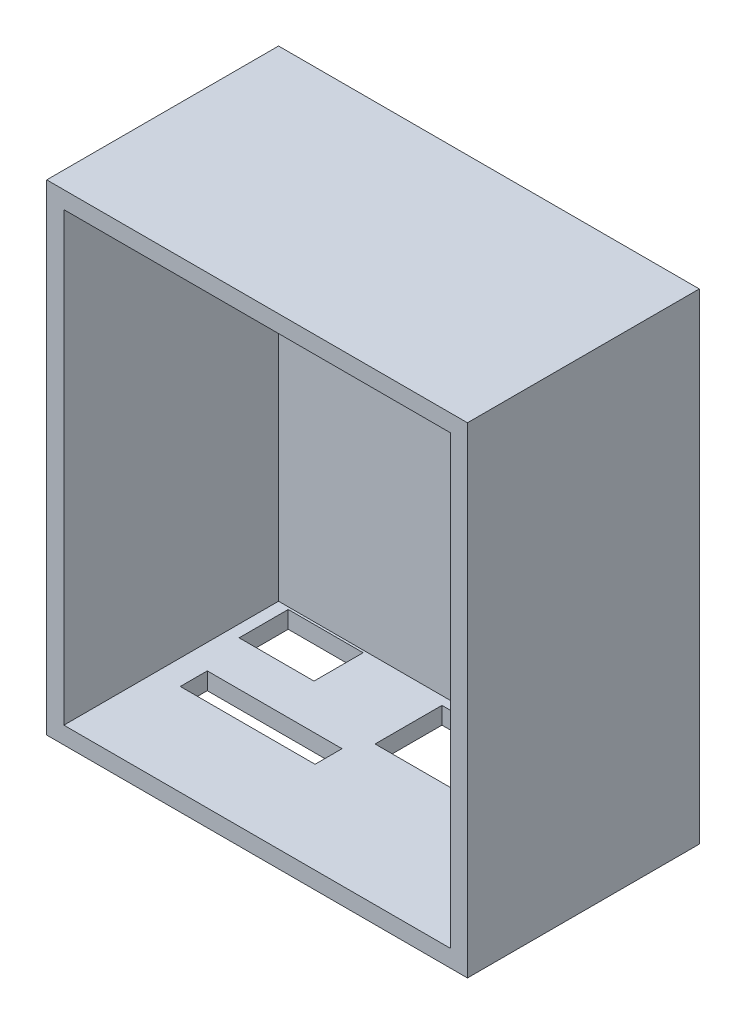
SolidWorks part; units mm, degrees
ref_plane "Piano frontale" through (0, 0, 0) normal (0, 0, 1) x (1, 0, 0)
ref_plane "Piano superiore" through (0, 0, 0) normal (0, 1, 0) x (1, 0, 0)
ref_plane "Piano destro" through (0, 0, 0) normal (1, 0, 0) x (0, 0, -1)
sketch "Schizzo1" plane through (0, 0, 0) normal (0, 0, 1) x (1, 0, 0)
  line L1 (0, 0) -> (49, 0)
  line L2 (0, 0) -> (0, 56)
  line L3 (0, 56) -> (49, 56)
  line L4 (49, 0) -> (49, 56)
  dimension "D1" = 49
  dimension "D2" = 56
extrude "Estrusione-Estrusione1" add sketch "Schizzo1" along normal blind 2
sketch "Schizzo3" plane through (0, 0, 2) normal (0, 0, 1) x (1, 0, 0)
  line L0 (49, 0) -> (49, 56) construction
  line L1 (0, 56) -> (49, 56)
  line L2 (0, 56) -> (0, 54)
  line L3 (0, 54) -> (49, 54)
  line L4 (49, 56) -> (49, 54)
  dimension "D1" = 2
extrude "Estrusione-Estrusione2" add sketch "Schizzo3" along normal blind 25
sketch "Schizzo4" plane through (0, 0, 2) normal (0, 0, 1) x (1, 0, 0)
  line L0 (0, 0) -> (49, 0) construction
  line L1 (49, 54) -> (47, 54)
  line L2 (49, 54) -> (49, 0)
  line L3 (49, 0) -> (47, 0)
  line L4 (47, 54) -> (47, 0)
  dimension "D1" = 2
extrude "Estrusione-Estrusione3" add sketch "Schizzo4" along normal blind 25
sketch "Schizzo5" plane through (0, 0, 2) normal (0, 0, 1) x (1, 0, 0)
  line L0 (0, 54) -> (0, 0) construction
  line L1 (47, 0) -> (0, 0)
  line L2 (47, 0) -> (47, 2)
  line L3 (47, 2) -> (0, 2)
  line L4 (0, 0) -> (0, 2)
  dimension "D1" = 2
extrude "Estrusione-Estrusione4" add sketch "Schizzo5" along normal blind 25
sketch "Schizzo6" plane through (0, 0, 2) normal (0, 0, 1) x (1, 0, 0)
  line L0 (47, 2) -> (0, 2) construction
  line L1 (0, 54) -> (2, 54)
  line L2 (0, 54) -> (0, 2)
  line L3 (0, 2) -> (2, 2)
  line L4 (2, 54) -> (2, 2)
  dimension "D1" = 2
extrude "Estrusione-Estrusione5" add sketch "Schizzo6" along normal blind 25
sketch "Schizzo7" plane through (0, 0, 2) normal (0, 0, 1) x (1, 0, 0)
  line L1 (2, 2) -> (2, 54) construction
  line L4 (2, 43.7) -> (27, 43.7)
  line L5 (2, 43.7) -> (2, 46.7)
  line L6 (2, 46.7) -> (27, 46.7)
  line L7 (27, 43.7) -> (27, 46.7)
  dimension "D2" = 3
  dimension "D3" = 25
extrude "Estrusione-Estrusione6" add sketch "Schizzo7" along normal blind 13.3
sketch "Schizzo9" plane through (0, 0, 2) normal (0, 0, 1) x (1, 0, 0)
  line L0 (2, 54) -> (47, 54) construction
  line L1 (47, 2) -> (43.5, 2)
  line L2 (47, 2) -> (47, 54)
  line L3 (47, 54) -> (43.5, 54)
  line L4 (43.5, 2) -> (43.5, 54)
  dimension "D1" = 3.5
extrude "Estrusione-Estrusione7" add sketch "Schizzo9" along normal blind 13.3
sketch "Schizzo10" plane through (0, 0, 15.3) normal (0, 0, 1) x (1, 0, 0)
  line L5 (4, 45.95) -> (8, 45.95)
  line L6 (4, 45.95) -> (4, 44.45)
  line L7 (4, 44.45) -> (8, 44.45)
  line L8 (8, 45.95) -> (8, 44.45)
  line L11 (26, 45.95) -> (22, 45.95)
  line L12 (26, 45.95) -> (26, 44.45)
  line L13 (26, 44.45) -> (22, 44.45)
  line L14 (22, 45.95) -> (22, 44.45)
  point P17 (26, 45.2)
  dimension "D3" = 1.5
  dimension "D4" = 4
  dimension "D6" = 4
extrude "Taglio-Estrusione1" cut sketch "Schizzo10" against normal blind 6
sketch "Schizzo11" plane through (0, 0, 15.3) normal (0, 0, 1) x (1, 0, 0)
  line L4 (46, 45.95) -> (44.5, 45.95)
  line L5 (46, 45.95) -> (46, 44.45)
  line L6 (46, 44.45) -> (44.5, 44.45)
  line L7 (44.5, 45.95) -> (44.5, 44.45)
  dimension "D2" = 1.5
  dimension "D3" = 1.5
extrude "Taglio-Estrusione2" cut sketch "Schizzo11" against normal blind 6
sketch "Schizzo12" plane through (0, 45.95, 0) normal (0, -1, 0) x (-1, 0, 0)
  line L0 (-8, -9.3) -> (-8, -15.3) construction
  line L1 (-4, -15.3) -> (-8, -15.3)
  line L2 (-4, -15.3) -> (-4, -14.3)
  line L3 (-4, -14.3) -> (-8, -14.3)
  line L4 (-8, -15.3) -> (-8, -14.3)
  dimension "D1" = 1
extrude "Taglio-Estrusione3" cut sketch "Schizzo12" against normal blind 0.75
sketch "Schizzo13" plane through (0, 44.45, 0) normal (0, 1, 0) x (1, 0, 0)
  line L0 (8, -9.3) -> (8, -15.3) construction
  line L1 (4, -15.3) -> (8, -15.3)
  line L2 (4, -15.3) -> (4, -14.3)
  line L3 (4, -14.3) -> (8, -14.3)
  line L4 (8, -15.3) -> (8, -14.3)
  dimension "D1" = 1
extrude "Taglio-Estrusione4" cut sketch "Schizzo13" against normal blind 0.75
sketch "Schizzo14" plane through (0, 45.95, 0) normal (0, -1, 0) x (-1, 0, 0)
  line L0 (-26, -9.3) -> (-26, -15.3) construction
  line L1 (-22, -15.3) -> (-26, -15.3)
  line L2 (-22, -15.3) -> (-22, -14.3)
  line L3 (-22, -14.3) -> (-26, -14.3)
  line L4 (-26, -15.3) -> (-26, -14.3)
  dimension "D1" = 1
extrude "Taglio-Estrusione5" cut sketch "Schizzo14" against normal blind 0.75
sketch "Schizzo15" plane through (0, 44.45, 0) normal (0, 1, 0) x (1, 0, 0)
  line L0 (26, -9.3) -> (26, -15.3) construction
  line L1 (22, -15.3) -> (26, -15.3)
  line L2 (22, -15.3) -> (22, -14.3)
  line L3 (22, -14.3) -> (26, -14.3)
  line L4 (26, -15.3) -> (26, -14.3)
  dimension "D1" = 1
extrude "Taglio-Estrusione6" cut sketch "Schizzo15" against normal blind 0.75
sketch "Schizzo21" plane through (0, 0, 15.3) normal (0, 0, 1) x (1, 0, 0)
  line L0 (43.5, 54) -> (43.5, 2) construction
  line L1 (44.5, 45.95) -> (43.5, 45.95)
  line L2 (44.5, 45.95) -> (44.5, 44.45)
  line L3 (44.5, 44.45) -> (43.5, 44.45)
  line L4 (43.5, 45.95) -> (43.5, 44.45)
extrude "Taglio-Estrusione7" cut sketch "Schizzo21" against normal blind 1
sketch "Schizzo23" plane through (0, 0, 15.3) normal (0, 0, 1) x (1, 0, 0)
  line L1 (43.5, 45.95) -> (46, 45.95)
  line L2 (43.5, 45.95) -> (43.5, 46.7)
  line L3 (43.5, 46.7) -> (46, 46.7)
  line L4 (46, 45.95) -> (46, 46.7)
  dimension "D1" = 0.75
extrude "Taglio-Estrusione8" cut sketch "Schizzo23" against normal blind 1
sketch "Schizzo24" plane through (0, 0, 15.3) normal (0, 0, 1) x (1, 0, 0)
  line L1 (43.5, 44.45) -> (45.9968, 44.45)
  line L2 (43.5, 44.45) -> (43.5, 43.7)
  line L3 (43.5, 43.7) -> (45.9968, 43.7)
  line L4 (45.9968, 44.45) -> (45.9968, 43.7)
  dimension "D1" = 0.75
extrude "Taglio-Estrusione9" cut sketch "Schizzo24" against normal blind 1
sketch "Schizzo26" plane through (0, 0, 15.3) normal (0, 0, 1) x (1, 0, 0)
  line L0 (47, 54) -> (47, 2) construction
  line L1 (45.9968, 43.7) -> (47, 43.7)
  line L2 (45.9968, 43.7) -> (45.9968, 46.7)
  line L3 (45.9968, 46.7) -> (47, 46.7)
  line L4 (47, 43.7) -> (47, 46.7)
  dimension "D1" = 3
extrude "Taglio-Estrusione10" cut sketch "Schizzo26" against normal blind 1
sketch "Schizzo27" plane through (0, 0, 15.3) normal (0, 0, 1) x (1, 0, 0)
  line L1 (26, 46.7) -> (27, 46.7)
  line L2 (26, 46.7) -> (26, 43.7)
  line L3 (26, 43.7) -> (27, 43.7)
  line L4 (27, 46.7) -> (27, 43.7)
extrude "Taglio-Estrusione11" cut sketch "Schizzo27" against normal blind 1
sketch "Schizzo28" plane through (0, 0, 15.3) normal (0, 0, 1) x (1, 0, 0)
  line L1 (47, 2) -> (47, 43.7) construction
  line L2 (43.5, 43.7) -> (43.5, 2) construction
  line L3 (47, 13.3) -> (43.5, 13.3)
  line L4 (47, 13.3) -> (47, 17.3)
  line L5 (47, 17.3) -> (43.5, 17.3)
  line L6 (43.5, 13.3) -> (43.5, 17.3)
  line L7 (47, 17.3) -> (26, 17.3) construction
extrude "Taglio-Estrusione12" cut sketch "Schizzo28" against normal blind 1
sketch "Schizzo33" plane through (0, 0, 15.3) normal (0, 0, 1) x (1, 0, 0)
  line L1 (43.5, 43.7) -> (43.5, 17.3) construction
  line L3 (43.5, 28.5) -> (47, 28.5)
  line L4 (43.5, 28.5) -> (43.5, 32.5)
  line L5 (43.5, 32.5) -> (47, 32.5)
  line L6 (47, 28.5) -> (47, 32.5)
extrude "Taglio-Estrusione16" cut sketch "Schizzo33" against normal blind 1
sketch "Schizzo34" plane through (0, 0, 0) normal (0, -1, 0) x (1, 0, 0)
  line L1 (3.3938, 7.9878) -> (12.1185, 7.9878)
  line L2 (3.3938, 7.9878) -> (3.3938, 2.267)
  line L3 (3.3938, 2.267) -> (12.1185, 2.267)
  line L4 (12.1185, 7.9878) -> (12.1185, 2.267)
extrude "Taglio-Estrusione17" cut sketch "Schizzo34" against normal blind 2
sketch "Schizzo36" plane through (0, 0, 0) normal (0, -1, 0) x (1, 0, 0)
  line L1 (22.0157, 10.7757) -> (40.2471, 10.7757)
  line L2 (22.0157, 10.7757) -> (22.0157, 2.9855)
  line L3 (22.0157, 2.9855) -> (40.2471, 2.9855)
  line L4 (40.2471, 10.7757) -> (40.2471, 2.9855)
extrude "Taglio-Estrusione18" cut sketch "Schizzo36" against normal blind 2
sketch "Schizzo37" plane through (0, 0, 0) normal (0, -1, 0) x (-1, 0, 0)
  line L1 (-4.8742, -16.3178) -> (-20.5692, -16.3178)
  line L2 (-4.8742, -16.3178) -> (-4.8742, -13.1741)
  line L3 (-4.8742, -13.1741) -> (-20.5692, -13.1741)
  line L4 (-20.5692, -16.3178) -> (-20.5692, -13.1741)
extrude "Taglio-Estrusione19" cut sketch "Schizzo37" against normal blind 2
